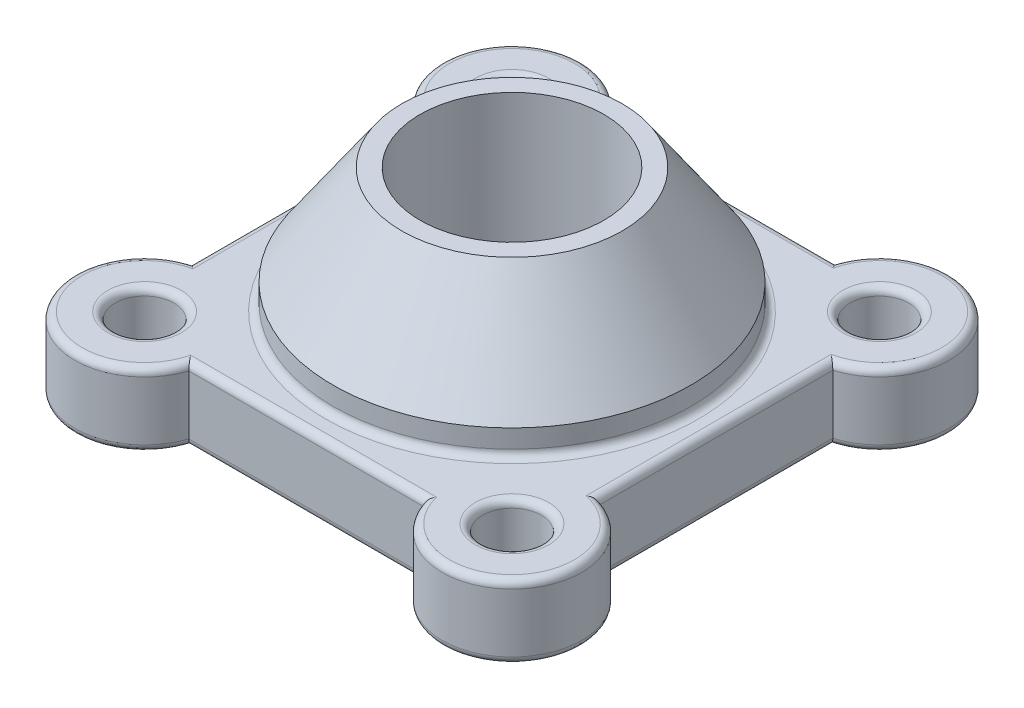
SolidWorks part; units mm, degrees
ref_plane "Front Plane" through (0, 0, 0) normal (0, 0, 1) x (1, 0, 0)
ref_plane "Top Plane" through (0, 0, 0) normal (0, 1, 0) x (1, 0, 0)
ref_plane "Right Plane" through (0, 0, 0) normal (1, 0, 0) x (0, 0, -1)
sketch "Sketch1" plane through (0, 0, 0) normal (0, 1, 0) x (1, 0, 0)
  line L1 (0, 0) -> (55.5, 0)
  line L2 (0, 0) -> (0, 56)
  line L3 (0, 56) -> (55.5, 56)
  line L4 (55.5, 0) -> (55.5, 56)
  dimension "D1" = 55.5
  dimension "D2" = 56
extrude "Boss-Extrude1" add sketch "Sketch1" along normal blind 10 contours L2 L3 L4 L1
sketch "Sketch2" plane through (0, 10, 0) normal (0, 1, 0) x (1, 0, 0)
  line L0 (0, 0) -> (55.5, 0) construction
  line L1 (0, 0) -> (0, 56) construction
  line L2 (55.5, 0) -> (55.5, 56) construction
  circle A0 centre (2.75, 3) radius 9.5
  circle A1 centre (2.75, 3) radius 4
  circle A2 centre (52.75, 3) radius 9.5
  circle A3 centre (52.75, 3) radius 4
  circle A4 centre (52.75, 53) radius 9.5
  circle A5 centre (52.75, 53) radius 4
  circle A6 centre (2.75, 53) radius 9.5
  circle A7 centre (2.75, 53) radius 4
  line M1 (0, 0) -> (55.5, 0)
  line M2 (55.5, 0) -> (55.5, 56)
  line M3 (55.5, 56) -> (0, 56)
  line M4 (0, 56) -> (0, 0)
  dimension "D3" = 8
  dimension "D4" = 9.5
  dimension "D2" = 2.75
  dimension "D7" = 50
  dimension "D8" = 50
  dimension "D9" = 3
  dimension "D10" = 2.75
  dimension "D11" = 3
  dimension "D5" = 2
  dimension "D6" = 2
extrude "Boss-Extrude2" add sketch "Sketch2" against normal blind 10 contours A1 A0 M4 M1 | A7 A6 M3 M4 | A5 A4 M2 M3 | A3 A2 M1 M2 region at (-0.2624, 10, -8.999) region at (-3.8715, 10, -59.4412) region at (46.9202, 10, 0.2624) region at (54.2276, 10, -62.1187)
extrude "Cut-Extrude1" cut sketch "Sketch2<3>" against normal blind 10 contours A5 M3 M2 | A3 M2 M1 | A1 M1 M4 | A7 M4 M3 region at (3.1426, 10, -3.2966) region at (3.1426, 10, -52.7034) region at (52.3574, 10, -3.2966) region at (52.3574, 10, -52.7034)
sketch "Sketch2<3>" plane through (0, 10, 0) normal (0, 1, 0) x (1, 0, 0) same geometry as "Sketch2"
fillet "Fillet1" radius 1 12 edges at (27.75, 10, 0) (-4.0596, 10, 3.6241) (0, 10, -28) (-4.0596, 10, -59.6241) (27.75, 10, -56) (59.5596, 10, -59.6241) (55.5, 10, -28) (59.5596, 10, 3.6241) (52.75, 10, -49) (52.75, 10, 1) (2.75, 10, 1) (2.75, 10, -49)
ref_plane "Plane1" through (0, 0, -28) normal (0, 0, 1) x (1, 0, 0)
sketch "Sketch3" plane through (0, 0, -28) normal (0, 0, 1) x (1, 0, 0)
  line L0 (40.25, 10) -> (52.1, 10)
  line L1 (11.0114, 10) -> (44.4886, 10) construction
  line L2 (61.25, 10) -> (44.4886, 10) construction
  line L3 (52.1, 10) -> (52.1, 13.5)
  line L4 (52.1, 13.5) -> (42.7522, 27)
  line L5 (42.7522, 27) -> (40.25, 27)
  line L6 (40.25, 27) -> (40.25, 10)
  line L7 (27.75, -3.8346) -> (27.75, 27.1439) construction
  line L8 (11.7639, 0) -> (43.7361, 0) construction
  dimension "D1" = 27.75
  dimension "D2" = 12.5
  dimension "D3" = 34.7
  dimension "D4" = 24.35
  dimension "D5" = 27
  dimension "D6" = 13.5
revolve "Revolve1" add sketch "Sketch3" angle 360 about L7
fillet "Fillet2" radius 1 13 edges at (2.75, 0, 1) (2.75, 0, -49) (52.75, 0, -49) (52.75, 0, 1) (59.5596, 0, -59.6241) (27.75, 0, -56) (-4.0596, 0, -59.6241) (0, 0, -28) (-4.0596, 0, 3.6241) (27.75, 0, 0) (59.5596, 0, 3.6241) (55.5, 0, -28) (27.75, 10, -3.65)
sketch "Sketch4" plane through (0, 27, 0) normal (0, 1, 0) x (1, 0, 0)
  line L0 (-4.4, 28) -> (4.4, 28) construction
  circle A0 centre (27.75, 28) radius 12.5
  circle A1 centre (27.75, 28) radius 12.5 construction
extrude "Cut-Extrude2" cut sketch "Sketch4" against normal up to surface (27 mm away) up to face at (2.75, 0, 2)
